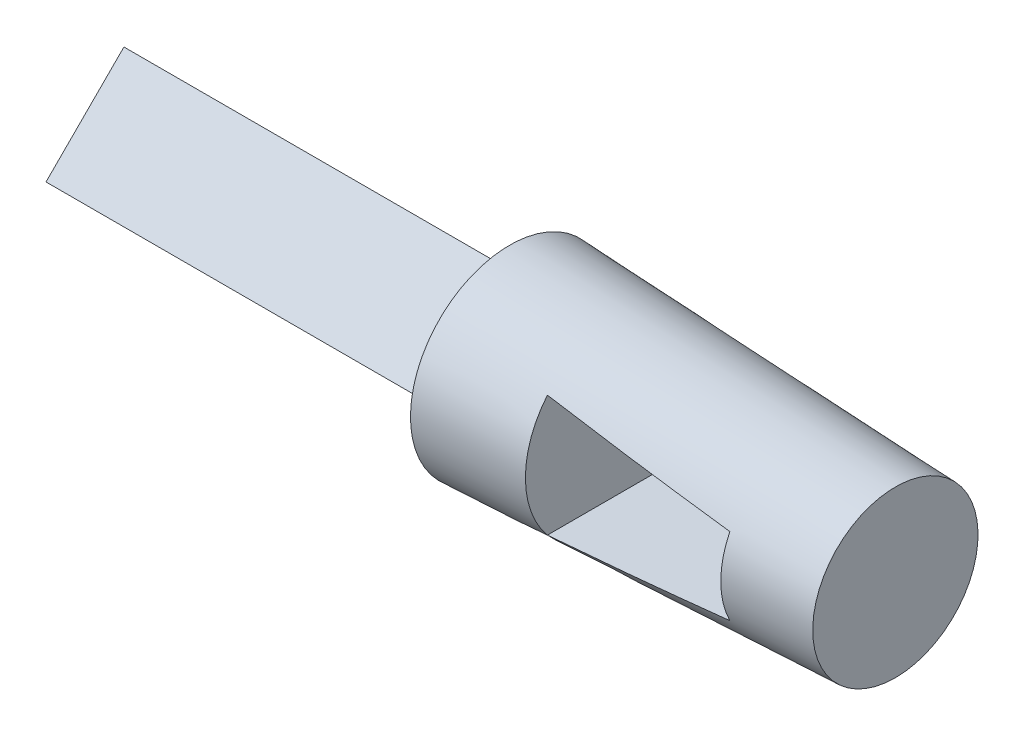
SolidWorks part; units mm, degrees
ref_plane "Спереди" through (0, 0, 0) normal (0, 0, 1) x (1, 0, 0)
ref_plane "Сверху" through (0, 0, 0) normal (0, 1, 0) x (1, 0, 0)
ref_plane "Справа" through (0, 0, 0) normal (1, 0, 0) x (0, 0, -1)
sketch "Эскиз1" plane through (0, 0, 0) normal (1, 0, 0) x (0, 0, -1)
  line L0 (0, 0) -> (0, 16.0126) construction
  line L1 (0, 0) -> (16.2734, 0) construction
  line L2 (0, 7.0711) -> (7.0711, 0)
  line L3 (0, 0) -> (-12.9811, 12.9811) construction
  line L4 (-7.0711, 0) -> (0, -7.0711)
  line L5 (-7.0711, 0) -> (0, 7.0711)
  line L6 (7.0711, 0) -> (0, -7.0711)
  line L7 (-0.0711, 7) -> (0.0711, 7)
  dimension "D1" = 45
  dimension "D3" = 10
extrude "Бобышка-Вытянуть1" add sketch "Эскиз1" along normal blind 35 contours L2 L6 L4 L5
sketch "Эскиз2" plane through (0, 0, 0) normal (0, 0, 1) x (1, 0, 0)
  line L0 (35, 0) -> (35, -7.0711) construction
  line L1 (35, 0) -> (35, 7.0711) construction
  line L2 (35, 0) -> (35, -7.0711) construction
  line L3 (35, 0) -> (35, 7.0711) construction
  line L4 (35, 0) -> (70, 0) construction
  line L5 (70, 0) -> (70, 7.5)
  line L6 (70, 7.5) -> (35, 9)
  line L7 (35, 9) -> (35, 0)
  line L8 (35, 0) -> (70, 0)
  dimension "D1" = 35
  dimension "D2" = 7.5
  dimension "D3" = 9
revolve "Повернуть1" add sketch "Эскиз2" angle 360 about L8
sketch "Эскиз3" plane through (0, 0, 0) normal (0, 0, 1) x (1, 0, 0)
  line L0 (70, -7.5) -> (70, 7.5) construction
  line L1 (70, -7.5) -> (70, 7.5)
  line L2 (70, 0) -> (35, 0) construction
  line L3 (35, 9) -> (35, -9) construction
  line L5 (45, -5.5) -> (45, 5.5)
  line L6 (45, 5.5) -> (62, 3.5)
  line L7 (62, 3.5) -> (62, -3.5)
  line L8 (45, -5.5) -> (62, -3.5)
  point P10 (62, 0)
  dimension "D1" = 11
  dimension "D2" = 8
  dimension "D3" = 17
  dimension "D4" = 7
extrude "Вырез-Вытянуть1" cut sketch "Эскиз3" against normal blind 35 and the other way blind 35 contours L8 L7 L6 L5
sketch "Эскиз4" plane through (0, 0, 0) normal (0, 0, 1) x (1, 0, 0)
  line L1 (0, 0) -> (0, 7.0711) construction
  line L4 (35, 0) -> (0, 0) construction
  line L6 (0, 0) -> (13.4434, 0)
  line L7 (0, 3.9985) -> (-2.0448, 0)
  line L8 (0, 2.5) -> (0, 3.9985)
  line L9 (13.4434, 0) -> (-9.2389, 0) construction
  line L10 (-2.0448, 0) -> (0, 0)
  line L11 (0, 2.5) -> (12, 2.5)
  line L12 (12, 2.5) -> (13.4434, 0)
  dimension "D1" = 2.5
  dimension "D2" = 12
revolve "Вырез-Повернуть3" cut sketch "Эскиз4" angle 360 about L9
